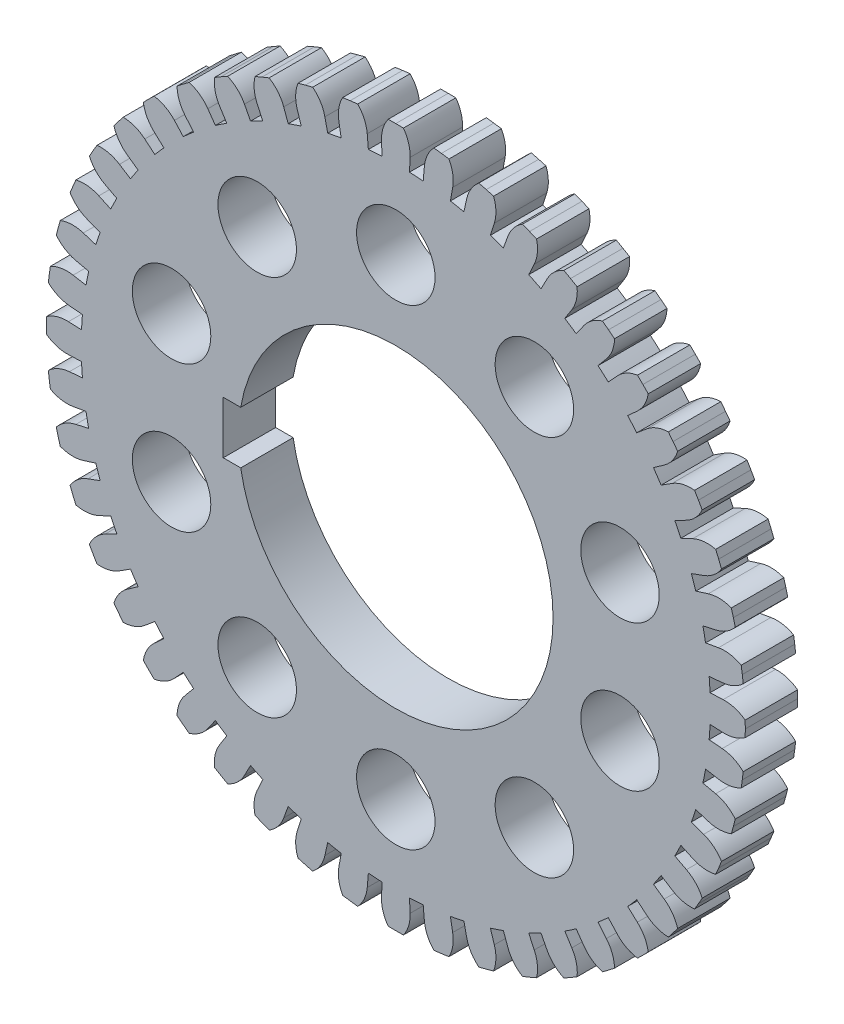
SolidWorks part; units mm, degrees
ref_plane "Plan de face" through (0, 0, 0) normal (0, 0, 1) x (1, 0, 0)
ref_plane "Plan de dessus" through (0, 0, 0) normal (0, 1, 0) x (1, 0, 0)
ref_plane "Plan de droite" through (0, 0, 0) normal (1, 0, 0) x (0, 0, -1)
sketch "Esquisse1" plane through (0, 0, 0) normal (0, 0, 1) x (1, 0, 0)
  line L0 (0, 0) -> (20, 0) construction
  line L1 (0, 0) -> (17.9315, 1.5688) construction
  line L2 (0, 0) -> (19.981, 0.8724) construction
  line L3 (19.981, 0.8724) -> (0, 0) construction
  line L4 (0, 0) -> (19.9952, 0.4363) construction
  line L5 (17.9829, 0.7851) -> (18.7322, 0.8179)
  line L6 (20, 0) -> (19.9952, 0.4363)
  line L7 (17.9829, -0.7851) -> (18.7322, -0.8179)
  line L8 (20, 0) -> (19.9952, -0.4363)
  line L9 (17.9315, 1.5688) -> (0, 0)
  line L10 (0, 0) -> (17.9315, -1.5688)
  circle A0 centre (0, 0) radius 18 construction
  circle A1 centre (0, 0) radius 18.75 construction
  circle A2 centre (0, 0) radius 20 construction
  arc A3 (18.7322, 0.8179) -> (19.9952, 0.4363) centre (18.8192, -1.1754) cw
  arc A4 (17.9315, 1.5688) -> (17.9829, 0.7851) centre (0, 0) cw
  arc A5 (17.9315, -1.5688) -> (17.9829, -0.7851) centre (0, 0) ccw
  arc A6 (18.7322, -0.8179) -> (19.9952, -0.4363) centre (18.8192, 1.1754) ccw
  dimension "D2" = 37.5
  dimension "D3" = 40
  dimension "D1" = 36
  dimension "D4" = 1.25
  dimension "D5" = 2.5
  dimension "D6" = 5
extrude "Boss.-Extru.3" add sketch "Esquisse1" along normal blind 3
pattern_circular "Répétition circulaire1" count 48 over 360 about axis through (0, 0, 3) along (0, 0, -1) of "Boss.-Extru.3"
sketch "Esquisse2" plane through (0, 0, 0) normal (0, 0, -1) x (-1, 0, 0)
  line L0 (0, 9) -> (0, 17.9829) construction
  line L1 (-0.7851, 17.9829) -> (0.7851, 17.9829) construction
  circle A0 centre (0, 0) radius 9
  circle A1 centre (0, 13.4914) radius 2.2457
  circle A2 centre (7.9301, 10.9148) radius 2.2457
  circle A3 centre (12.8311, 4.1691) radius 2.2457
  circle A4 centre (12.8311, -4.1691) radius 2.2457
  circle A5 centre (7.9301, -10.9148) radius 2.2457
  circle A6 centre (0, -13.4914) radius 2.2457
  circle A7 centre (-7.9301, -10.9148) radius 2.2457
  circle A8 centre (-12.8311, -4.1691) radius 2.2457
  circle A9 centre (-12.8311, 4.1691) radius 2.2457
  circle A10 centre (-7.9301, 10.9148) radius 2.2457
  point P13 (0, 13.4914)
  point P33 (0, 0)
  dimension "D1" = 18
  dimension "D3" = 4.4914
  dimension "D2" = 8.9829
  dimension "D4" = 10
extrude "Enlèv. mat.-Extru.1" cut sketch "Esquisse2" against normal up to surface (3 mm away) up to face at (0, 0, 3)
sketch "Esquisse3" plane through (0, 0, 3) normal (0, 0, 1) x (1, 0, 0)
  line L1 (-9.8741, -1.5) -> (-8.8741, -1.5)
  line L2 (-9.8741, -1.5) -> (-9.8741, 1.5)
  line L3 (-9.8741, 1.5) -> (-8.8741, 1.5)
  line L5 (-9.8741, -1.5) -> (-8.8741, 1.5) construction
  line L6 (-9.8741, 1.5) -> (-8.8741, -1.5) construction
  circle A0 centre (0, 0) radius 9 construction
  arc A1 (-8.8741, 1.5) -> (-8.8741, -1.5) centre (0, 0) ccw
  point P0 (-9.3741, 0)
  dimension "D1" = 3
  dimension "D2" = 1
extrude "Enlèv. mat.-Extru.2" cut sketch "Esquisse3" against normal up to surface (3 mm away) up to face at (10.5854, -4.1691, 0)
equation "\"D5@Esquisse1\"=\"D6@Esquisse1\"/2"
equation "\"D4@Esquisse1\"=\"D6@Esquisse1\"/4"
equation "\"D3@Esquisse2\"=1/2 * \"D2@Esquisse2\""
